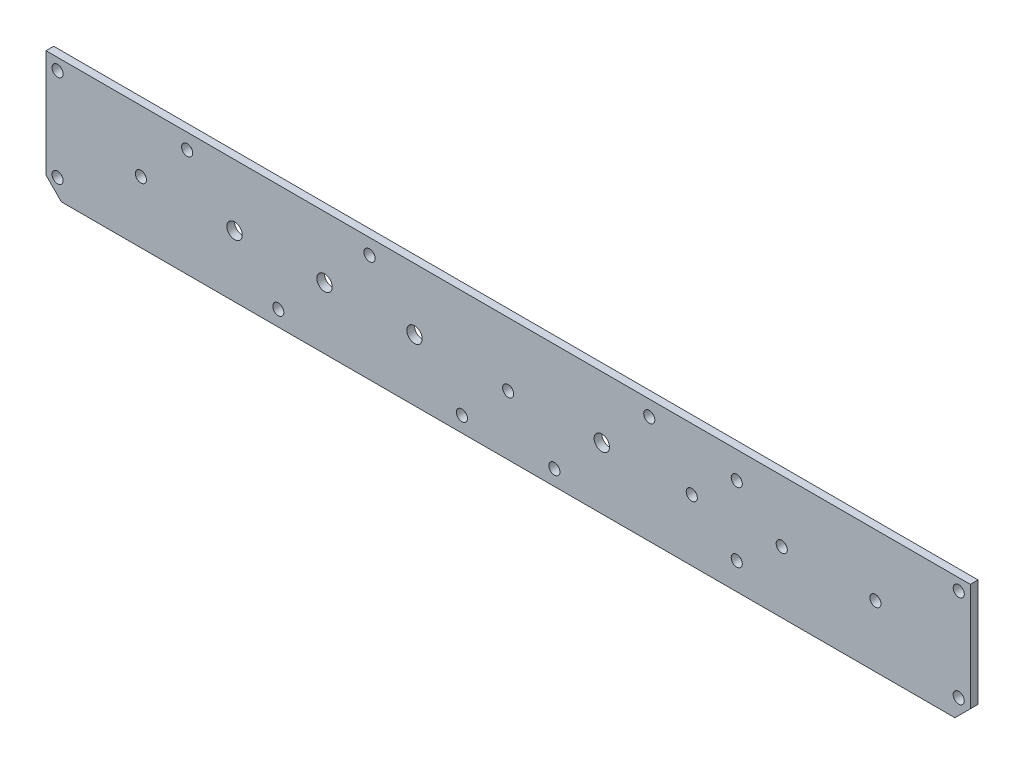
SolidWorks part; units mm, degrees
ref_plane "Front Plane" through (0, 0, 0) normal (0, 0, 1) x (1, 0, 0)
ref_plane "Top Plane" through (0, 0, 0) normal (0, 1, 0) x (1, 0, 0)
ref_plane "Right Plane" through (0, 0, 0) normal (1, 0, 0) x (0, 0, -1)
sketch "Sketch1" plane through (0, 0, 0) normal (0, 0, 1) x (1, 0, 0)
  line L1 (0, 0) -> (381, 0)
  line L2 (0, 0) -> (0, 50.8)
  line L3 (0, 50.8) -> (381, 50.8)
  line L4 (381, 0) -> (381, 50.8)
  dimension "D1" = 50.8
  dimension "D2" = 381
extrude "Boss-Extrude1" add sketch "Sketch1" along normal blind 3.175
sketch "Sketch2" plane through (0, 0, 3.175) normal (0, 0, 1) x (1, 0, 0)
  line L1 (190.5, 50.8) -> (190.5, 0) construction
  line L2 (381, 50.8) -> (0, 50.8) construction
  line L3 (0, 0) -> (381, 0) construction
  line L4 (266.192, 25.4) -> (303.276, 25.4) construction
  line L5 (0, 6.35) -> (0, 0)
  line L6 (0, 50.8) -> (0, 0) construction
  line L7 (0, 0) -> (6.35, 0)
  line L8 (6.35, 0) -> (0, 6.35)
  line L9 (381, 0) -> (374.65, 0)
  line L10 (374.65, 0) -> (381, 6.35)
  line L11 (381, 6.35) -> (381, 0)
  circle A0 centre (39.116, 25.4) radius 2.286
  circle A1 centre (190.5, 24.6062) radius 2.286
  circle A2 centre (114.808, 25.4) radius 3.175
  circle A3 centre (77.724, 25.4) radius 3.175
  circle A4 centre (151.892, 25.4) radius 3.175
  circle A5 centre (229.108, 25.4) radius 3.175
  circle A6 centre (303.276, 25.4) radius 2.286
  circle A7 centre (266.192, 25.4) radius 2.286
  circle A8 centre (341.884, 25.4) radius 2.286
  circle A9 centre (58.166, 44.45) radius 2.286
  circle A10 centre (171.45, 6.35) radius 2.286
  circle A11 centre (209.55, 6.35) radius 2.286
  circle A13 centre (133.35, 44.45) radius 2.286
  circle A14 centre (248.666, 44.45) radius 2.286
  circle A15 centre (95.758, 6.35) radius 2.286
  circle A19 centre (4.7625, 46.0375) radius 2.286
  circle A20 centre (4.7625, 7.9375) radius 2.286
  circle A21 centre (376.2375, 7.9375) radius 2.286
  circle A22 centre (376.2375, 46.0375) radius 2.286
  circle A25 centre (284.734, 11.1125) radius 2.286
  circle A26 centre (284.734, 39.6875) radius 2.286
  point P17 (190.5, 25.4)
  point P38 (0, 0)
  point P48 (0, 0)
  point P49 (284.734, 25.4)
  dimension "D2" = 4.572
  dimension "D5" = 6.35
  dimension "D7" = 4.572
  dimension "D12" = 4.572
  dimension "D15" = 4.572
  dimension "D16" = 4.572
  dimension "D19" = 4.572
  dimension "D21" = 6.35
  dimension "D27" = 4.572
  dimension "D29" = 11.1125
  dimension "D8" = 4.572
  dimension "D3" = 38.608
  dimension "D4" = 0.7937
  dimension "D6" = 14.2875
  dimension "D20" = 19.05
  dimension "D22" = 6.35
  dimension "D25" = 4.7625
  dimension "D26" = 4.7625
  dimension "D28" = 7.9375
extrude "Cut-Extrude1" cut sketch "Sketch2" against normal up to next
